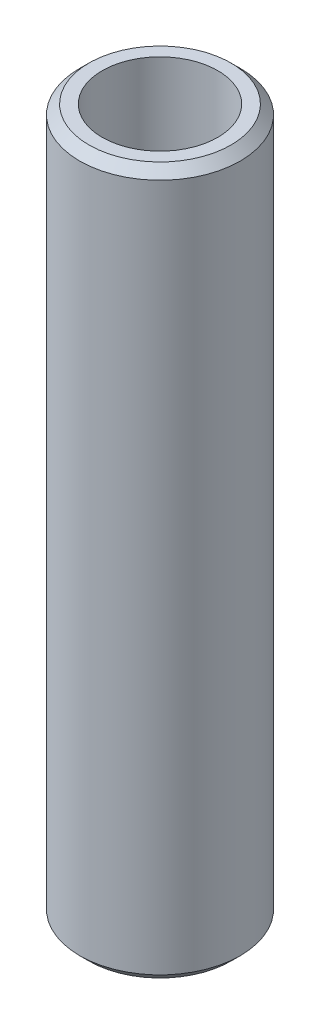
SolidWorks part; units mm, degrees
ref_plane "Front Plane" through (0, 0, 0) normal (0, 0, 1) x (1, 0, 0)
ref_plane "Top Plane" through (0, 0, 0) normal (0, 1, 0) x (1, 0, 0)
ref_plane "Right Plane" through (0, 0, 0) normal (1, 0, 0) x (0, 0, -1)
sketch "Sketch1" plane through (0, 0, 0) normal (0, 1, 0) x (1, 0, 0)
  circle A0 centre (0, 0) radius 30
  dimension "SHAFT_OD" = 60
extrude "Boss-Extrude1" add sketch "Sketch1" along normal blind 264.0164
sketch "Sketch2" plane through (0, 0, 0) normal (0, 1, 0) x (1, 0, 0)
  circle A0 centre (0, 0) radius 21.5936
  dimension "BORE_D" = 43.1872
extrude "Cut-Extrude1" cut sketch "Sketch2" along normal through all
chamfer "Chamfer1" distance 3.4604 angle 45 2 edges at (0, 264.0164, 30) (0, 0, 30)
